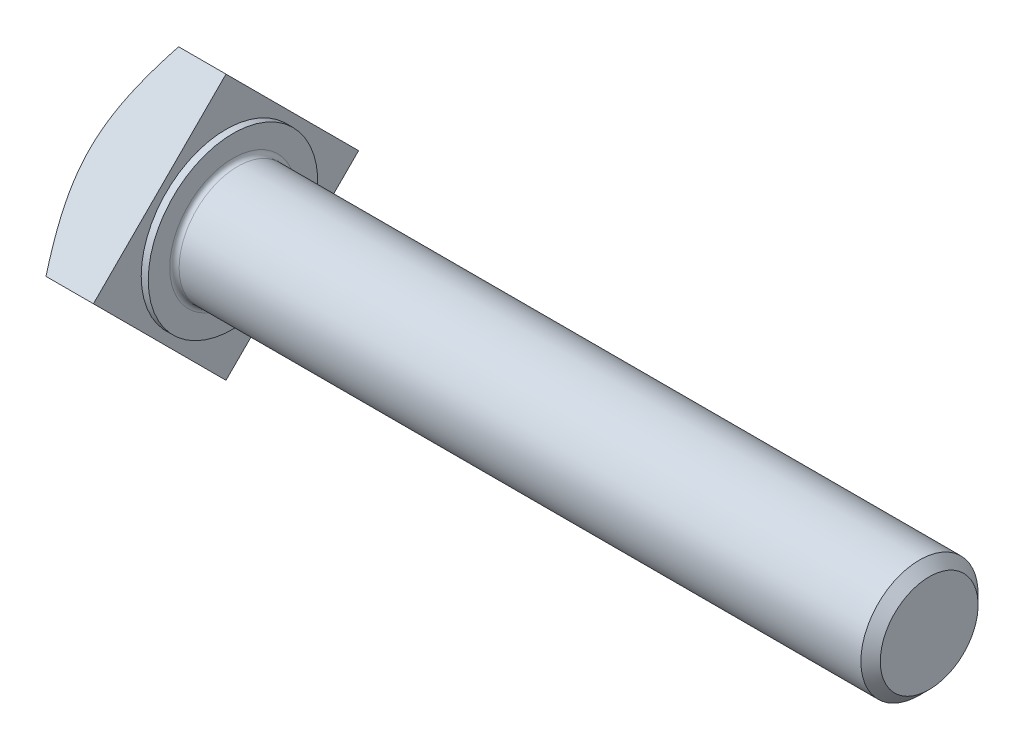
SolidWorks part; units mm, degrees
ref_plane "Front Plane" through (0, 0, 0) normal (0, 0, 1) x (1, 0, 0)
ref_plane "Top Plane" through (0, 0, 0) normal (0, 1, 0) x (1, 0, 0)
ref_plane "Right Plane" through (0, 0, 0) normal (1, 0, 0) x (0, 0, -1)
sketch "BaseHeadSke" plane through (0, 0, 0) normal (1, 0, 0) x (0, 0, -1)
  line L0 (-33.7114, 0) -> (29.9357, 0) construction
  line L1 (0, 35.0598) -> (0, -29.1266) construction
  line L2 (0, 11.3137) -> (11.3137, 0)
  line L3 (11.3137, 0) -> (0, -11.3137)
  line L4 (0, -11.3137) -> (-11.3137, 0)
  line L5 (-11.3137, 0) -> (0, 11.3137)
  dimension "Head_sidewidth" = 16
extrude "BaseHead" add sketch "BaseHeadSke" along normal blind 6.4
sketch "BodySke" plane through (0, 0, 0) normal (0, 0, 1) x (1, 0, 0)
  line L0 (0, 0) -> (81.8774, 0) construction
  line L1 (6.4, 0) -> (6.4, 7.235)
  line L2 (6.4, 11.3137) -> (6.4, 0) construction
  line L3 (6.4, 7.235) -> (7, 7.235)
  line L4 (7, 7.235) -> (7, 5)
  line L5 (7, 5) -> (65.572, 5)
  line L6 (65.572, 5) -> (66.4, 4.172)
  line L7 (66.4, 4.172) -> (66.4, 0)
  line L8 (66.4, 0) -> (6.4, 0)
  line L9 (7.9, 0) -> (7.9, 9.1784) construction
  line L10 (8.5, 0) -> (8.5, 9.1784) construction
  dimension "Advance" = 1.5
  dimension "Thread_minor" = 8.344
revolve "BaseBody" add sketch "BodySke" angle 360 about L0
cosmetic thread "ThreadCosmetic" [suppressed] parameters "Thread_length"=26, "Thread_minor"=8.344
fillet "Fillet1" radius 0.4 1 edges at (7, 0, 5)
sketch "HeadChamferSke" plane through (0, 0, 0) normal (0, 0, 1) x (1, 0, 0)
  line L0 (0, 0) -> (67.5964, 0) construction
  line L1 (0, 11.3137) -> (0, 7.235)
  line L2 (0, 7.235) -> (2.3548, 11.3137)
  line L3 (2.3548, 11.3137) -> (0, 11.3137)
  line L4 (6.4, 11.3137) -> (0, 11.3137) construction
  line L5 (0, 11.3137) -> (0, 0) construction
  dimension "Head_chamfer_angle" = 30
revolve "HeadChamfer" cut sketch "HeadChamferSke" angle 360 about L0
sketch "ThdSchSke" plane through (0, 0, 0) normal (0, 0, 1) x (1, 0, 0)
  line L0 (0, 0) -> (70.3562, 0) construction
  line L1 (0, 0) -> (81.8774, 0) construction
  line L2 (64.072, 5.9561) -> (64.072, 5)
  line L3 (64.072, 5.9561) -> (65.0281, 5.9561)
  line L4 (65.0281, 5.9561) -> (65.0281, 5)
  line L5 (65.0281, 5) -> (64.55, 4.172)
  line L6 (64.55, 4.172) -> (64.072, 5)
  dimension "D1" = 1.5
revolve "ThreadSchematic" [suppressed] cut sketch "ThdSchSke" angle 360 about L0
pattern_linear "ThdSchPat" [suppressed] of bodies 116
equation "\"D1@ThdSchSke\" = \"Advance@BodySke\""
equation "\"Tooth_Num@ThdSchPat\" =  int( (  \"Length@BodySke\" - \"Distance@BodySke\" - \"Bearing_depth@BodySke\" )  / \"Advance@BodySke\" ) "
equation "\"Advance@ThdSchPat\" = \"Advance@BodySke\""
equation "\"Thread_minor@ThreadCosmetic\" = \"Thread_minor@BodySke\""
